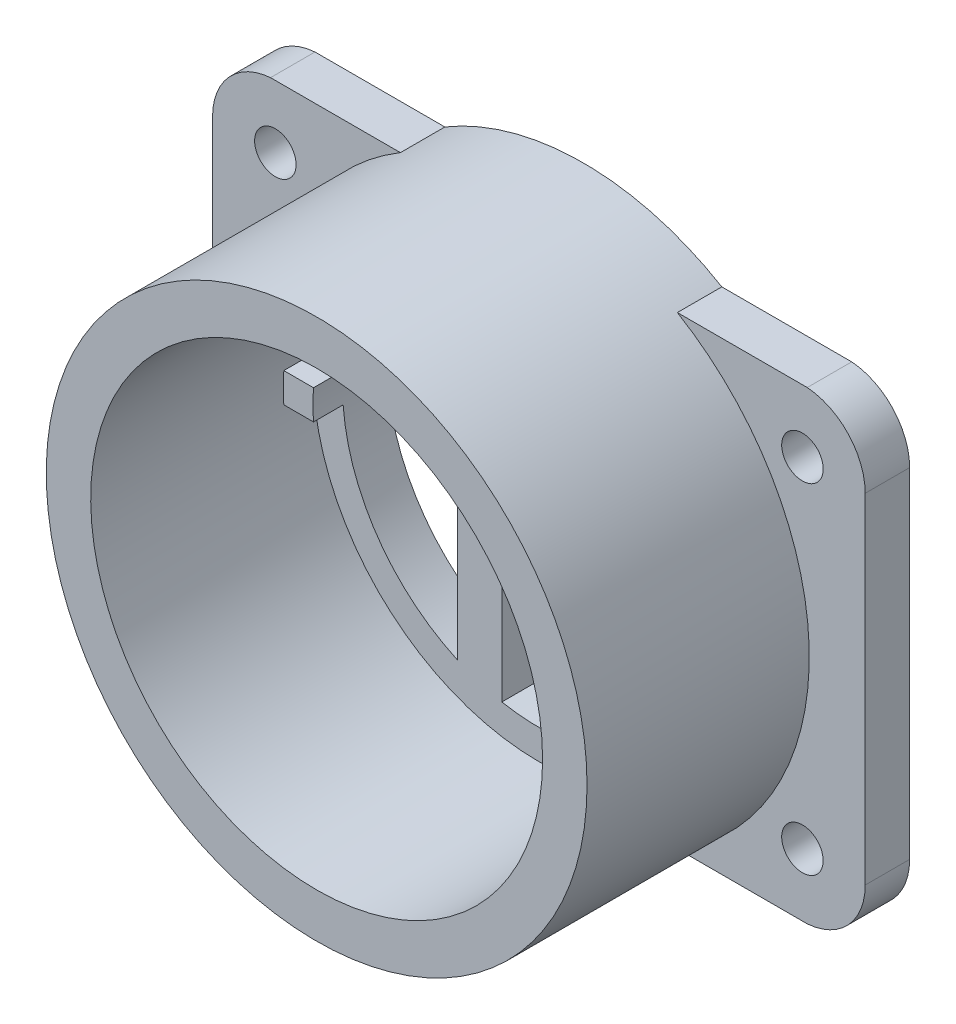
SolidWorks part; units mm, degrees
ref_plane "Front Plane" through (0, 0, 0) normal (0, 0, 1) x (1, 0, 0)
ref_plane "Top Plane" through (0, 0, 0) normal (0, 1, 0) x (1, 0, 0)
ref_plane "Right Plane" through (0, 0, 0) normal (1, 0, 0) x (0, 0, -1)
sketch "Sketch1" plane through (0, 0, 0) normal (0, 0, 1) x (1, 0, 0)
  line L4 (18.1127, 15.675) -> (-18.1127, 15.675)
  line L5 (-22.025, 11.45) -> (-22.025, -11.45)
  line L6 (-18.1127, -15.675) -> (18.1127, -15.675)
  line L7 (22.025, -11.45) -> (22.025, 11.45)
  line L8 (18.1127, 15.675) -> (-18.1127, 15.675)
  line L9 (-22.025, 11.45) -> (-22.025, -11.45)
  line L10 (-18.1127, -15.675) -> (18.1127, -15.675)
  line L11 (22.025, -11.45) -> (22.025, 11.45)
  circle A0 centre (-17.7875, -11.45) radius 1.4 construction
  circle A1 centre (-17.7875, 11.45) radius 1.4 construction
  circle A2 centre (17.7875, 11.45) radius 1.4 construction
  circle A3 centre (17.7875, -11.45) radius 1.4 construction
  arc A4 (-18.1127, 15.675) -> (-22.025, 11.45) centre (-17.7875, 11.45) ccw
  arc A5 (-22.025, -11.45) -> (-18.1127, -15.675) centre (-17.7875, -11.45) ccw
  arc A6 (18.1127, -15.675) -> (22.025, -11.45) centre (17.7875, -11.45) ccw
  arc A7 (22.025, 11.45) -> (18.1127, 15.675) centre (17.7875, 11.45) ccw
  arc A8 (-18.1127, 15.675) -> (-22.025, 11.45) centre (-17.7875, 11.45) ccw
  arc A9 (-22.025, -11.45) -> (-18.1127, -15.675) centre (-17.7875, -11.45) ccw
  arc A10 (18.1127, -15.675) -> (22.025, -11.45) centre (17.7875, -11.45) ccw
  arc A11 (22.025, 11.45) -> (18.1127, 15.675) centre (17.7875, 11.45) ccw
  circle A12 centre (-17.7875, -11.45) radius 1.4
  circle A13 centre (-17.7875, 11.45) radius 1.4
  circle A14 centre (17.7875, 11.45) radius 1.4
  circle A15 centre (17.7875, -11.45) radius 1.4
  circle A16 centre (0, 0) radius 15.25
  circle A17 centre (0, 0) radius 18.25
  circle A18 centre (0, 0) radius 13.25
  dimension "D2" = 30.5
  dimension "D3" = 3
  dimension "D4" = 26.5
  dimension "D1" = 0
extrude "Boss-Extrude1" add sketch "Sketch1" along normal blind 3 contours A17 L8 A8 L9 A9 L10 A12 A13 | L8 A17 L10 A16 | L8 A17 | L10 A17 | A16 | A17 L10 A10 L11 A11 L8 A15 A14 region at (18.268, 0, 0) region at (15.4504, 8.7759, 0) region at (0, 16.7115, 0) region at (-18.268, 0, 0) region at (0, -16.7115, 0) region at (-14.8187, 0, 0)
sketch "Sketch3" plane through (0, 0, 3) normal (0, 0, 1) x (1, 0, 0)
  circle A0 centre (0, 0) radius 18.25
  arc A1 (9.3465, 15.675) -> (-9.3465, 15.675) centre (0, 0) ccw construction
  circle A2 centre (0, 0) radius 15.25
  dimension "D1" = 30.5
extrude "Boss-Extrude2" add sketch "Sketch3" along normal blind 15
sketch "Sketch4" plane through (0, 0, 3) normal (0, 0, 1) x (1, 0, 0)
  line L0 (-15.4939, 15.0131) -> (-12.6325, 13.1712)
  line L1 (-17.7875, 11.45) -> (0, 0) construction
  line L2 (-20.0811, 7.8869) -> (-17.2198, 6.045)
  line L3 (0, 18.25) -> (0, -18.25) construction
  line L4 (-18.25, 0) -> (18.25, 0) construction
  line L5 (15.4939, 15.0131) -> (12.6325, 13.1712)
  line L6 (20.0811, 7.8869) -> (17.2198, 6.045)
  line L7 (20.0811, -7.8869) -> (17.2198, -6.045)
  line L8 (15.4939, -15.0131) -> (12.6325, -13.1712)
  line L9 (-15.4939, -15.0131) -> (-12.6325, -13.1712)
  line L10 (-20.0811, -7.8869) -> (-17.2198, -6.045)
  line L11 (19.5375, 8.7314) -> (16.3081, 8.5752)
  line L12 (-19.2669, 14.3248) -> (-21.0169, 11.6062)
  line L13 (-21.0169, 11.6062) -> (-19.5375, 8.7314)
  line L14 (-19.5375, 8.7314) -> (-16.3081, 8.5752)
  line L15 (-16.3081, 8.5752) -> (-14.5581, 11.2938)
  line L16 (-14.5581, 11.2938) -> (-16.0375, 14.1686)
  line L17 (-16.0375, 14.1686) -> (-19.2669, 14.3248)
  line L18 (16.3081, 8.5752) -> (14.5581, 11.2938)
  line L19 (14.5581, 11.2938) -> (16.0375, 14.1686)
  line L20 (16.0375, 14.1686) -> (19.2669, 14.3248)
  line L21 (19.2669, 14.3248) -> (21.0169, 11.6062)
  line L22 (21.0169, 11.6062) -> (19.5375, 8.7314)
  line L23 (-14.5581, -11.2938) -> (-16.0375, -14.1686)
  line L24 (-16.3081, -8.5752) -> (-14.5581, -11.2938)
  line L25 (-19.5375, -8.7314) -> (-16.3081, -8.5752)
  line L26 (-21.0169, -11.6062) -> (-19.5375, -8.7314)
  line L27 (-19.2669, -14.3248) -> (-21.0169, -11.6062)
  line L28 (-16.0375, -14.1686) -> (-19.2669, -14.3248)
  line L29 (16.3081, -8.5752) -> (14.5581, -11.2938)
  line L30 (19.5375, -8.7314) -> (16.3081, -8.5752)
  line L31 (21.0169, -11.6062) -> (19.5375, -8.7314)
  line L32 (19.2669, -14.3248) -> (21.0169, -11.6062)
  line L33 (16.0375, -14.1686) -> (19.2669, -14.3248)
  line L34 (14.5581, -11.2938) -> (16.0375, -14.1686)
  circle A0 centre (-17.7875, 11.45) radius 4.2375
  arc A1 (-18.1127, 15.675) -> (-22.025, 11.45) centre (-17.7875, 11.45) ccw construction
  arc A2 (-9.3465, 15.675) -> (-9.3465, -15.675) centre (0, 0) ccw construction
  circle A3 centre (0, 0) radius 18.25 construction
  circle A4 centre (0, 0) radius 18.25
  circle A5 centre (17.7875, 11.45) radius 4.2375
  circle A6 centre (17.7875, -11.45) radius 4.2375
  circle A7 centre (-17.7875, -11.45) radius 4.2375
  circle A8 centre (-17.7875, 11.45) radius 2.8 construction
  arc M19 (-9.3465, -15.675) -> (-9.3465, 15.675) centre (0, 0) cw
  line M20 (-9.3465, 15.675) -> (-18.1127, 15.675)
  arc M21 (-18.1127, 15.675) -> (-22.025, 11.45) centre (-17.7875, 11.45) ccw
  arc M23 (-22.025, -11.45) -> (-18.1127, -15.675) centre (-17.7875, -11.45) ccw
  line M24 (-18.1127, -15.675) -> (-9.3465, -15.675)
  dimension "D1" = 5.6
extrude "Boss-Extrude3" [suppressed] add sketch "Sketch4" along normal blind 3 contours A0 L17 L16 L15 L14 L13 L12 M19 M20 M21 | A0 L0 M19 | A0 L2 M19 | A4 A5 L5 | A5 A4 L21 L22 L11 L18 L19 L20 | L6 A5 A4 | A6 L7 A4 | A6 A4 L34 L29 L30 L31 L32 L33 | A6 A4 L8 | A7 L9 M19 | A7 A4 L23 L28 L27 L26 L25 L24 M23 M24 | L10 A7 M19
sketch "Sketch5" plane through (0, 0, 3) normal (0, 0, 1) x (1, 0, 0)
  line L1 (-15.25, -1) -> (15.25, -1)
  line L2 (-15.25, -1) -> (-15.25, 1)
  line L3 (-15.25, 1) -> (15.25, 1)
  line L4 (15.25, -1) -> (15.25, 1)
  line L5 (-15.25, -1) -> (15.25, 1) construction
  line L6 (-15.25, 1) -> (15.25, -1) construction
  circle A0 centre (0, 0) radius 15.25 construction
  circle A1 centre (0, 0) radius 13.25 construction
  circle A2 centre (0, 0) radius 13.25
  point P0 (0, 0)
  circle M3 centre (0, 0) radius 13.25
  circle M4 centre (0, 0) radius 15.25
  dimension "D1" = 2
extrude "Boss-Extrude4" add sketch "Sketch5" along normal blind 2 contours L3 L1 M4 M3 | L3 L1 M3 M4 region at (-14.2382, 0, 3) region at (14.2382, 0, 3)
sketch "Sketch6" plane through (0, 0, 0) normal (0, 0, -1) x (-1, 0, 0)
  line L0 (0, 13.25) -> (0, -13.25) construction
  line L1 (-4, 12.6318) -> (-4, -12.6318) construction
  line L2 (5.5, -13.012) -> (2.5, -13.012)
  line L3 (-5.5, -13.012) -> (-2.5, -13.012)
  line L4 (-5.5, -13.012) -> (-5.5, 13.012)
  line L5 (-5.5, 13.012) -> (-2.5, 13.012)
  line L6 (-2.5, -13.012) -> (-2.5, 13.012)
  line L7 (-5.5, -13.012) -> (-2.5, 13.012) construction
  line L8 (-5.5, 13.012) -> (-2.5, -13.012) construction
  line L9 (2.5, -13.012) -> (2.5, 13.012)
  line L10 (5.5, 13.012) -> (2.5, 13.012)
  line L11 (5.5, -13.012) -> (5.5, 13.012)
  circle A0 centre (0, 0) radius 13.25 construction
  circle A1 centre (0, 0) radius 13.25
  point P7 (-4, 0)
  circle M24 centre (0, 0) radius 13.25
  dimension "D1" = 4
  dimension "D2" = 3
extrude "Boss-Extrude5" add sketch "Sketch6" against normal up to surface (3 mm away) contours L6 L4 M24 | L11 L9 M24 region at (-3.9811, 0, 0) region at (3.9811, 0, 0) up to face at (0, 7.625, 3)
